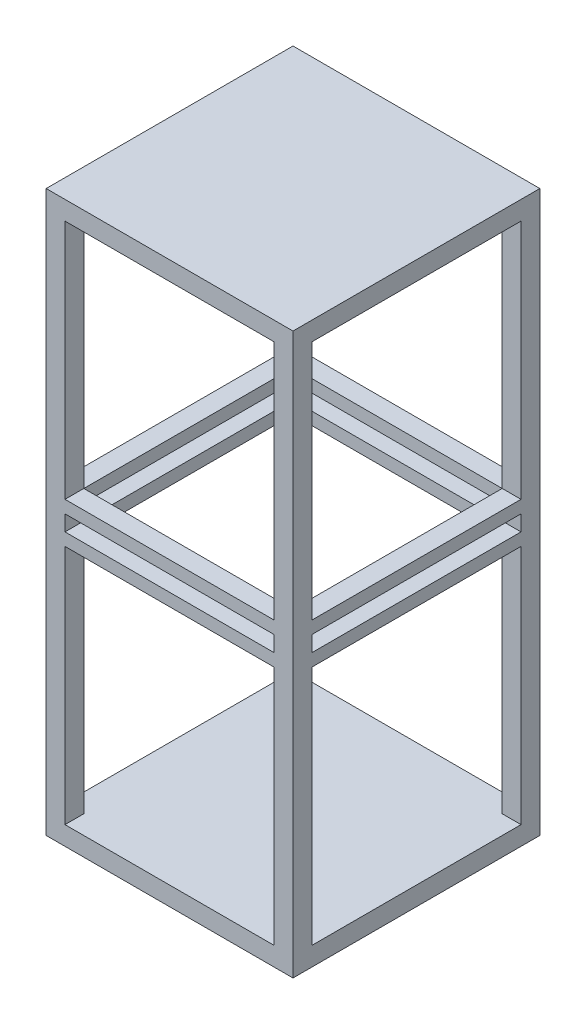
SolidWorks part; units mm, degrees
ref_plane "Front" through (0, 0, 0) normal (0, 0, 1) x (1, 0, 0)
ref_plane "Top" through (0, 0, 0) normal (0, 1, 0) x (1, 0, 0)
ref_plane "Right" through (0, 0, 0) normal (1, 0, 0) x (0, 0, -1)
sketch "Sketch1" plane through (0, 0, 0) normal (0, 1, 0) x (1, 0, 0)
  line L1 (0, 0) -> (100, 0)
  line L2 (0, 0) -> (0, 100)
  line L3 (0, 100) -> (100, 100)
  line L4 (100, 0) -> (100, 100)
  dimension "D1" = 100
  dimension "D2" = 100
extrude "Boss-Extrude1" add sketch "Sketch1" along normal blind 227
sketch "Sketch6" plane through (100, 0, 0) normal (1, 0, 0) x (0, 0, -1)
  line L8 (0, 227) -> (0, 0) construction
  line L9 (7.62, 105.245) -> (92.38, 105.245)
  line L10 (7.62, 105.245) -> (7.62, 7.62)
  line L11 (7.62, 7.62) -> (92.38, 7.62)
  line L12 (92.38, 105.245) -> (92.38, 7.62)
  line L13 (0, 0) -> (100, 0) construction
  line L15 (100, 227) -> (100, 0) construction
  line L16 (7.62, 116.675) -> (92.38, 116.675)
  line L17 (7.62, 116.675) -> (7.62, 110.325)
  line L18 (7.62, 110.325) -> (92.38, 110.325)
  line L19 (92.38, 116.675) -> (92.38, 110.325)
  line L20 (0, 227) -> (100, 227) construction
  line L21 (7.62, 219.38) -> (92.38, 219.38)
  line L22 (7.62, 219.38) -> (7.62, 121.755)
  line L23 (7.62, 121.755) -> (92.38, 121.755)
  line L24 (92.38, 219.38) -> (92.38, 121.755)
  dimension "D1" = 97.625
  dimension "D2" = 7.62
  dimension "D3" = 7.62
  dimension "D4" = 7.62
  dimension "D5" = 7.62
  dimension "D6" = 5.08
  dimension "D7" = 7.62
  dimension "D8" = 6.35
  dimension "D9" = 7.62
  dimension "D10" = 7.62
  dimension "D11" = 97.625
extrude "Cut-Extrude3" cut sketch "Sketch6" against normal through all
sketch "Sketch10" plane through (0, 0, 0) normal (0, 0, 1) x (1, 0, 0)
  line L0 (0, 227) -> (0, 0) construction
  line L1 (7.62, 219.38) -> (92.38, 219.38)
  line L2 (7.62, 219.38) -> (7.62, 121.755)
  line L3 (7.62, 121.755) -> (92.38, 121.755)
  line L4 (92.38, 219.38) -> (92.38, 121.755)
  line L5 (7.62, 116.675) -> (92.38, 116.675)
  line L6 (7.62, 116.675) -> (7.62, 110.325)
  line L7 (7.62, 110.325) -> (92.38, 110.325)
  line L8 (92.38, 116.675) -> (92.38, 110.325)
  line L9 (7.62, 105.245) -> (92.38, 105.245)
  line L10 (7.62, 105.245) -> (7.62, 7.62)
  line L11 (7.62, 7.62) -> (92.38, 7.62)
  line L12 (92.38, 105.245) -> (92.38, 7.62)
  line L13 (0, 227) -> (100, 227) construction
  line L14 (100, 227) -> (100, 0) construction
  line L15 (0, 0) -> (100, 0) construction
  dimension "D1" = 7.62
  dimension "D2" = 7.62
  dimension "D3" = 7.62
  dimension "D4" = 7.62
  dimension "D5" = 7.62
  dimension "D6" = 7.62
  dimension "D7" = 7.62
  dimension "D8" = 7.62
  dimension "D9" = 5.08
  dimension "D10" = 5.08
  dimension "D11" = 6.35
extrude "Cut-Extrude4" cut sketch "Sketch10" against normal through all
sketch "Sketch11" plane through (0, 121.755, 0) normal (0, 1, 0) x (1, 0, 0)
  line L1 (7.62, 7.62) -> (92.38, 7.62)
  line L2 (7.62, 7.62) -> (7.62, 92.38)
  line L3 (7.62, 92.38) -> (92.38, 92.38)
  line L4 (92.38, 7.62) -> (92.38, 92.38)
extrude "Cut-Extrude5" cut sketch "Sketch11" against normal blind 25.4
sketch "Sketch13" plane through (100, 0, 0) normal (1, 0, 0) x (0, 0, -1)
  line L0 (7.62, 219.38) -> (0, 219.38) construction
  dimension "D1" = 7.62
sketch "Sketch14" plane through (0, 227, 0) normal (0, 1, 0) x (1, 0, 0)
  line L0 (0, 0) -> (0, 7.62) construction
  line L1 (0, 100) -> (0, 0) construction
  line L2 (0, 7.62) -> (7.62, 7.62) construction
  line L3 (100, 100) -> (100, 92.38) construction
  line L4 (100, 0) -> (100, 100) construction
  line L5 (100, 92.38) -> (92.38, 92.38) construction
  line L7 (7.62, 7.62) -> (92.38, 7.62)
  line L8 (7.62, 7.62) -> (7.62, 92.38)
  line L9 (7.62, 92.38) -> (92.38, 92.38)
  line L10 (92.38, 7.62) -> (92.38, 92.38)
